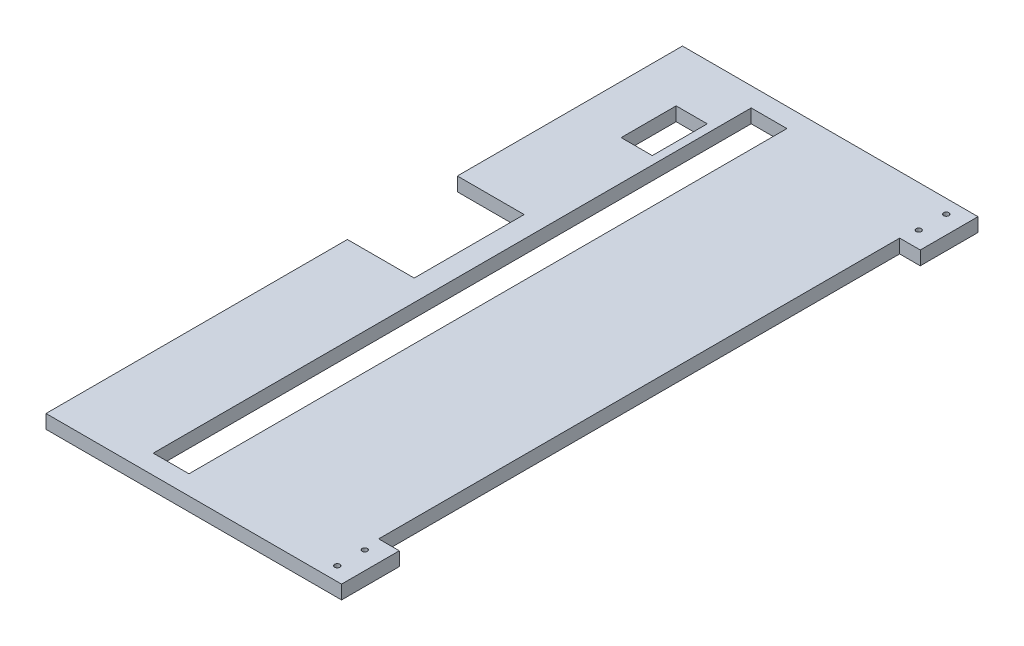
SolidWorks part; units mm, degrees
ref_plane "Front Plane" through (0, 0, 0) normal (0, 0, 1) x (1, 0, 0)
ref_plane "Top Plane" through (0, 0, 0) normal (0, 1, 0) x (1, 0, 0)
ref_plane "Right Plane" through (0, 0, 0) normal (1, 0, 0) x (0, 0, -1)
sketch "Sketch1" plane through (0, 0, 0) normal (0, 1, 0) x (1, 0, 0)
  line L1 (5911.0841, -8489.3124) -> (6341.0841, -8489.3124)
  line L2 (5911.0841, -8489.3124) -> (5911.0841, -8952.3124)
  line L3 (5911.0841, -8952.3124) -> (6341.0841, -8952.3124)
  line L4 (6341.0841, -8489.3124) -> (6341.0841, -8952.3124)
  dimension "D1" = 463
  dimension "D2" = 430
extrude "Boss-Extrude1" add sketch "Sketch1" along normal blind 10
sketch "Sketch2" plane through (0, 10, 0) normal (0, 1, 0) x (1, 0, 0)
  line L0 (5911.0841, -8489.3124) -> (5911.0841, -8952.3124) construction
  line L1 (5959.6841, -8733.0598) -> (5911.0841, -8733.0598)
  line L2 (5959.6841, -8733.0598) -> (5959.6841, -8653.0598)
  line L3 (5959.6841, -8653.0598) -> (5911.0841, -8653.0598)
  line L4 (5911.0841, -8733.0598) -> (5911.0841, -8653.0598)
  line L9 (6341.0841, -8952.3124) -> (6341.0841, -8489.3124) construction
  line L10 (6341.0841, -8733.3844) -> (6292.4841, -8733.3844)
  line L11 (6341.0841, -8733.3844) -> (6341.0841, -8653.3844)
  line L12 (6341.0841, -8653.3844) -> (6292.4841, -8653.3844)
  line L13 (6292.4841, -8733.3844) -> (6292.4841, -8653.3844)
  dimension "D1" = 48.6
  dimension "D2" = 80
  dimension "D3" = 80
  dimension "D4" = 48.6
extrude "Cut-Extrude1" cut sketch "Sketch2" against normal blind 10
sketch "Sketch3" plane through (0, 10, 0) normal (0, 1, 0) x (1, 0, 0)
  line L0 (5975.0841, -8541.6519) -> (5975.0841, -8938.3124)
  line L1 (6277.0841, -8938.3124) -> (6251.0841, -8938.3124)
  line L2 (6277.0841, -8938.3124) -> (6277.0841, -8503.3124)
  line L3 (6277.0841, -8503.3124) -> (6251.0841, -8503.3124)
  line L4 (6251.0841, -8938.3124) -> (6251.0841, -8503.3124)
  line L5 (5975.0841, -8503.3124) -> (6001.0841, -8503.3124)
  line L11 (5975.0841, -8938.3124) -> (6001.0841, -8938.3124)
  line L12 (6001.0841, -8503.3124) -> (6001.0841, -8938.3124)
  line L33 (5946.4841, -8529.3124) -> (5969.1312, -8529.3124)
  line L34 (5946.4841, -8529.3124) -> (5946.4841, -8569.3124)
  line L35 (5946.4841, -8569.3124) -> (5969.1312, -8569.3124)
  line L36 (5911.0841, -8733.0598) -> (5911.0841, -8952.3124) construction
  line L37 (6341.0841, -8952.3124) -> (6341.0841, -8733.3844) construction
  line L38 (5969.1312, -8529.3124) -> (5969.1312, -8569.3124)
  line L39 (6111.0841, -8531.3124) -> (6141.0841, -8531.3124)
  line L40 (6111.0841, -8531.3124) -> (6111.0841, -8910.3124)
  line L41 (6111.0841, -8910.3124) -> (6141.0841, -8910.3124)
  line L42 (6141.0841, -8531.3124) -> (6141.0841, -8910.3124)
  line L44 (6341.0841, -8489.3124) -> (5911.0841, -8489.3124) construction
  line L45 (5975.0841, -8503.3124) -> (5975.0841, -8541.6519)
  line L47 (5911.0841, -8952.3124) -> (6341.0841, -8952.3124) construction
  circle A0 centre (6112.9841, -8942.3124) radius 1.9
  circle A1 centre (6139.1841, -8942.3124) radius 1.9
  circle A2 centre (6112.9841, -8499.3124) radius 1.9
  circle A3 centre (6139.1841, -8499.3124) radius 1.9
  circle A4 centre (6112.9841, -8922.3124) radius 1.9
  circle A5 centre (6139.1841, -8922.3124) radius 1.9
  circle A6 centre (6112.9841, -8519.3124) radius 1.9
  circle A7 centre (6139.1841, -8519.3124) radius 1.9
  point P32 (6126.0841, -8489.3124)
  point P33 (6126.0841, -8531.3124)
  dimension "D12" = 10
  dimension "D13" = 10
  dimension "D15" = 42
  dimension "D16" = 20
  dimension "D18" = 20
  dimension "D1" = 26
  dimension "D2" = 435
  dimension "D3" = 26
  dimension "D4" = 435
  dimension "D5" = 10
  dimension "D6" = 64
  dimension "D7" = 40
  dimension "D8" = 64
  dimension "D9" = 30
  dimension "D10" = 379
  dimension "D11" = 110
  dimension "D14" = 10
  dimension "D17" = 20
  dimension "D19" = 20
  dimension "D20" = 14
  dimension "D21" = 14
extrude "Cut-Extrude2" cut sketch "Sketch3" against normal blind 10
sketch "Sketch4" plane through (0, 10, 0) normal (0, 1, 0) x (1, 0, 0)
  line L0 (6251.0841, -8503.3124) -> (6251.0841, -8938.3124) construction
  line L1 (6251.0841, -8898.0965) -> (6186.0841, -8898.0965)
  line L2 (6251.0841, -8898.0965) -> (6251.0841, -8833.0965)
  line L3 (6251.0841, -8833.0965) -> (6186.0841, -8833.0965)
  line L4 (6186.0841, -8898.0965) -> (6186.0841, -8833.0965)
  dimension "D1" = 65
  dimension "D2" = 65
extrude "Cut-Extrude3" cut sketch "Sketch4" against normal blind 10
ref_plane "Plane1" through (6126.0841, 0, 0) normal (-1, 0, 0) x (0, 0, 1)
sketch "Sketch5" plane through (6126.0841, 0, 0) normal (-1, 0, 0) x (0, 0, 1)
  line L1 (8395.6862, 142.8464) -> (9031.9061, 142.8464)
  line L2 (8395.6862, 142.8464) -> (8395.6862, -229.0644)
  line L3 (8395.6862, -229.0644) -> (9031.9061, -229.0644)
  line L4 (9031.9061, 142.8464) -> (9031.9061, -229.0644)
extrude "Cut-Extrude5" cut sketch "Sketch5" against normal blind 255
